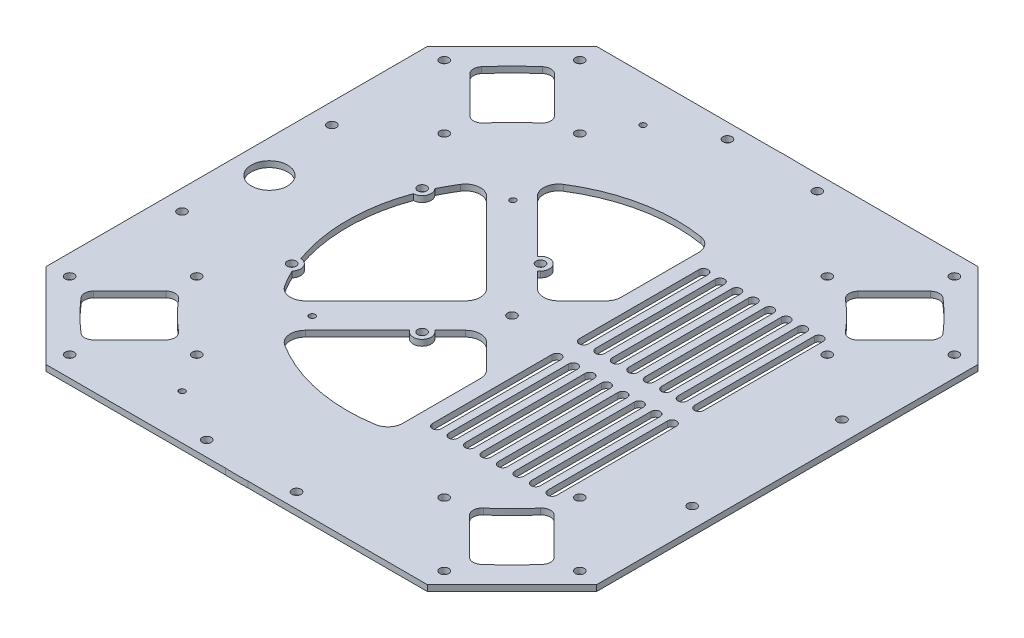
SolidWorks part; units mm, degrees
material "Thornel Mat VMA"
ref_plane "前视基准面" through (0, 0, 0) normal (0, 0, 1) x (1, 0, 0)
ref_plane "上视基准面" through (0, 0, 0) normal (0, 1, 0) x (1, 0, 0)
ref_plane "右视基准面" through (0, 0, 0) normal (1, 0, 0) x (0, 0, -1)
sketch "草图1" plane through (0, 0, 0) normal (0, 1, 0) x (1, 0, 0)
  line L0 (-63.6396, 91.9239) -> (-91.9239, 63.6396)
  line L1 (63.6396, 91.9239) -> (-63.6396, 91.9239)
  line L2 (91.9239, 63.6396) -> (91.9239, -63.6396)
  line L3 (63.6396, -91.9239) -> (-63.6396, -91.9239)
  line L4 (-91.9239, 63.6396) -> (-91.9239, -63.6396)
  line L5 (91.9239, 91.9239) -> (-91.9239, -91.9239) construction
  line L6 (91.9239, -91.9239) -> (-91.9239, 91.9239) construction
  line L7 (91.9239, -63.6396) -> (63.6396, -91.9239)
  line L8 (-91.9239, -63.6396) -> (-63.6396, -91.9239)
  line L9 (63.6396, 91.9239) -> (91.9239, 63.6396)
  line L10 (-91.9239, 91.9239) -> (-91.9239, -91.9239) construction
  line L11 (-91.9239, -91.9239) -> (91.9239, -91.9239) construction
  line L12 (91.9239, -91.9239) -> (91.9239, 91.9239) construction
  line L13 (91.9239, 91.9239) -> (-91.9239, 91.9239) construction
  point P0 (0, 0)
  dimension "D1" = 220
  dimension "D2" = 40
extrude "凸台-拉伸1" add sketch "草图1" along normal blind 2
sketch "草图15" plane through (0, 2, 0) normal (0, 1, 0) x (1, 0, 0)
  line L1 (-40.3412, 82.6837) -> (-31.9185, 62.6852)
  line L2 (44.6358, 80.4465) -> (36.2732, 60.2701)
  line L3 (-42.4295, -81.6317) -> (-34.5316, -61.2845)
  line L4 (41.391, -82.1632) -> (34.5498, -61.2743)
  arc A0 (-42.4295, -81.6317) -> (41.391, -82.1632) centre (0, 0) ccw
  arc A2 (-34.5316, -61.2845) -> (34.5498, -61.2743) centre (0, 0) ccw
  arc A3 (36.2732, 60.2701) -> (-31.9185, 62.6852) centre (0, 0) ccw
  arc A4 (44.6358, 80.4465) -> (-40.3412, 82.6837) centre (0, 0) ccw
  dimension "D1" = 92
extrude "凸台-拉伸3" add sketch "草图15" against normal up to surface (2 mm away) up to face at (0, 0, 0)
sketch "草图18" plane through (0, 2, 0) normal (0, 1, 0) x (1, 0, 0)
  line L0 (-44.0207, 0) -> (12.6253, 0) construction
  line L3 (-54.0207, 0) -> (-91.9239, 0) construction
  line L4 (-91.9239, 63.6396) -> (-91.9239, -63.6396) construction
  line L5 (-4.5, -10) -> (4.5, -10) construction
  line L9 (-4.5, 10) -> (4.5, -10) construction
  line L10 (-4.5, -10) -> (4.5, 10) construction
  line L11 (-4.5, 10) -> (4.5, 10) construction
  circle A9 centre (0, 0) radius 1.5
  point P3 (0, 0)
  point P15 (0, 0)
extrude "切除-拉伸5" cut sketch "草图18" against normal through all both and the other way through all
sketch "草图20" plane through (0, 0, 0) normal (0, -1, 0) x (1, 0, 0)
  line L0 (-45.8783, 0) -> (57.9239, 0) construction
  line L1 (57.9239, 44.5) -> (57.9239, 4.5) construction
  line L2 (59.4239, 44.5) -> (59.4239, 4.5)
  line L3 (56.4239, 44.5) -> (56.4239, 4.5)
  line L4 (57.9239, -44.5) -> (57.9239, -4.5) construction
  line L5 (59.4239, -44.5) -> (59.4239, -4.5)
  line L6 (56.4239, -44.5) -> (56.4239, -4.5)
  line L7 (52.4239, 44.5) -> (52.4239, 4.5) construction
  line L8 (53.9239, 44.5) -> (53.9239, 4.5)
  line L9 (50.9239, 44.5) -> (50.9239, 4.5)
  line L10 (52.4239, -44.5) -> (52.4239, -4.5) construction
  line L11 (53.9239, -44.5) -> (53.9239, -4.5)
  line L12 (50.9239, -44.5) -> (50.9239, -4.5)
  line L13 (46.9239, 44.5) -> (46.9239, 4.5) construction
  line L14 (48.4239, 44.5) -> (48.4239, 4.5)
  line L15 (45.4239, 44.5) -> (45.4239, 4.5)
  line L16 (46.9239, -44.5) -> (46.9239, -4.5) construction
  line L17 (48.4239, -44.5) -> (48.4239, -4.5)
  line L18 (45.4239, -44.5) -> (45.4239, -4.5)
  line L19 (41.4239, 44.5) -> (41.4239, 4.5) construction
  line L20 (42.9239, 44.5) -> (42.9239, 4.5)
  line L21 (39.9239, 44.5) -> (39.9239, 4.5)
  line L22 (41.4239, -44.5) -> (41.4239, -4.5) construction
  line L23 (42.9239, -44.5) -> (42.9239, -4.5)
  line L24 (39.9239, -44.5) -> (39.9239, -4.5)
  line L25 (35.9239, 44.5) -> (35.9239, 4.5) construction
  line L26 (37.4239, 44.5) -> (37.4239, 4.5)
  line L27 (34.4239, 44.5) -> (34.4239, 4.5)
  line L28 (35.9239, -44.5) -> (35.9239, -4.5) construction
  line L29 (37.4239, -44.5) -> (37.4239, -4.5)
  line L30 (34.4239, -44.5) -> (34.4239, -4.5)
  line L31 (30.4239, 44.5) -> (30.4239, 4.5) construction
  line L32 (31.9239, 44.5) -> (31.9239, 4.5)
  line L33 (28.9239, 44.5) -> (28.9239, 4.5)
  line L34 (30.4239, -44.5) -> (30.4239, -4.5) construction
  line L35 (31.9239, -44.5) -> (31.9239, -4.5)
  line L36 (28.9239, -44.5) -> (28.9239, -4.5)
  line L37 (24.9239, 44.5) -> (24.9239, 4.5) construction
  line L38 (26.4239, 44.5) -> (26.4239, 4.5)
  line L39 (23.4239, 44.5) -> (23.4239, 4.5)
  line L40 (24.9239, -44.5) -> (24.9239, -4.5) construction
  line L41 (26.4239, -44.5) -> (26.4239, -4.5)
  line L42 (23.4239, -44.5) -> (23.4239, -4.5)
  line L43 (19.4239, 44.5) -> (19.4239, 4.5) construction
  line L44 (20.9239, 44.5) -> (20.9239, 4.5)
  line L45 (17.9239, 44.5) -> (17.9239, 4.5)
  line L46 (19.4239, -44.5) -> (19.4239, -4.5) construction
  line L47 (20.9239, -44.5) -> (20.9239, -4.5)
  line L48 (17.9239, -44.5) -> (17.9239, -4.5)
  line L49 (91.9239, 63.6396) -> (91.9239, -63.6396) construction
  line L382 (13.9239, -44.5) -> (13.9239, -4.5) construction
  line L383 (12.4239, -44.5) -> (12.4239, -4.5) [skipped]
  line L384 (15.4239, -44.5) -> (15.4239, -4.5) [skipped]
  line L385 (13.9239, 44.5) -> (13.9239, 4.5) construction
  line L386 (15.4239, 44.5) -> (15.4239, 4.5) [skipped]
  line L387 (12.4239, 44.5) -> (12.4239, 4.5) [skipped]
  line L388 (13.9239, -44.5) -> (13.9239, -4.5) construction
  line L389 (12.4239, -44.5) -> (12.4239, -4.5) [skipped]
  line L390 (15.4239, -44.5) -> (15.4239, -4.5) [skipped]
  line L391 (13.9239, 44.5) -> (13.9239, 4.5) construction
  line L392 (15.4239, 44.5) -> (15.4239, 4.5) [skipped]
  line L393 (12.4239, 44.5) -> (12.4239, 4.5) [skipped]
  arc A0 (59.4239, 44.5) -> (56.4239, 44.5) centre (57.9239, 44.5) ccw
  arc A1 (56.4239, 4.5) -> (59.4239, 4.5) centre (57.9239, 4.5) ccw
  arc A2 (59.4239, -44.5) -> (56.4239, -44.5) centre (57.9239, -44.5) cw
  arc A3 (56.4239, -4.5) -> (59.4239, -4.5) centre (57.9239, -4.5) cw
  arc A4 (53.9239, 44.5) -> (50.9239, 44.5) centre (52.4239, 44.5) ccw
  arc A5 (50.9239, 4.5) -> (53.9239, 4.5) centre (52.4239, 4.5) ccw
  arc A6 (53.9239, -44.5) -> (50.9239, -44.5) centre (52.4239, -44.5) cw
  arc A7 (50.9239, -4.5) -> (53.9239, -4.5) centre (52.4239, -4.5) cw
  arc A8 (48.4239, 44.5) -> (45.4239, 44.5) centre (46.9239, 44.5) ccw
  arc A9 (45.4239, 4.5) -> (48.4239, 4.5) centre (46.9239, 4.5) ccw
  arc A10 (48.4239, -44.5) -> (45.4239, -44.5) centre (46.9239, -44.5) cw
  arc A11 (45.4239, -4.5) -> (48.4239, -4.5) centre (46.9239, -4.5) cw
  arc A12 (42.9239, 44.5) -> (39.9239, 44.5) centre (41.4239, 44.5) ccw
  arc A13 (39.9239, 4.5) -> (42.9239, 4.5) centre (41.4239, 4.5) ccw
  arc A14 (42.9239, -44.5) -> (39.9239, -44.5) centre (41.4239, -44.5) cw
  arc A15 (39.9239, -4.5) -> (42.9239, -4.5) centre (41.4239, -4.5) cw
  arc A16 (37.4239, 44.5) -> (34.4239, 44.5) centre (35.9239, 44.5) ccw
  arc A17 (34.4239, 4.5) -> (37.4239, 4.5) centre (35.9239, 4.5) ccw
  arc A18 (37.4239, -44.5) -> (34.4239, -44.5) centre (35.9239, -44.5) cw
  arc A19 (34.4239, -4.5) -> (37.4239, -4.5) centre (35.9239, -4.5) cw
  arc A20 (31.9239, 44.5) -> (28.9239, 44.5) centre (30.4239, 44.5) ccw
  arc A21 (28.9239, 4.5) -> (31.9239, 4.5) centre (30.4239, 4.5) ccw
  arc A22 (31.9239, -44.5) -> (28.9239, -44.5) centre (30.4239, -44.5) cw
  arc A23 (28.9239, -4.5) -> (31.9239, -4.5) centre (30.4239, -4.5) cw
  arc A24 (26.4239, 44.5) -> (23.4239, 44.5) centre (24.9239, 44.5) ccw
  arc A25 (23.4239, 4.5) -> (26.4239, 4.5) centre (24.9239, 4.5) ccw
  arc A26 (26.4239, -44.5) -> (23.4239, -44.5) centre (24.9239, -44.5) cw
  arc A27 (23.4239, -4.5) -> (26.4239, -4.5) centre (24.9239, -4.5) cw
  arc A28 (20.9239, 44.5) -> (17.9239, 44.5) centre (19.4239, 44.5) ccw
  arc A29 (17.9239, 4.5) -> (20.9239, 4.5) centre (19.4239, 4.5) ccw
  arc A30 (20.9239, -44.5) -> (17.9239, -44.5) centre (19.4239, -44.5) cw
  arc A31 (17.9239, -4.5) -> (20.9239, -4.5) centre (19.4239, -4.5) cw
  arc A258 (12.4239, -44.5) -> (15.4239, -44.5) centre (13.9239, -44.5) ccw [skipped]
  arc A259 (15.4239, -4.5) -> (12.4239, -4.5) centre (13.9239, -4.5) ccw [skipped]
  arc A260 (15.4239, 44.5) -> (12.4239, 44.5) centre (13.9239, 44.5) ccw [skipped]
  arc A261 (12.4239, 4.5) -> (15.4239, 4.5) centre (13.9239, 4.5) ccw [skipped]
  point P5 (57.9239, 24.5)
  point P11 (57.9239, 3)
  point P13 (57.9239, -24.5)
  point P18 (57.9239, -3)
  point P19 (79.1207, 0)
  point P23 (52.4239, 24.5)
  point P29 (52.4239, 3)
  point P31 (52.4239, -24.5)
  point P36 (52.4239, -3)
  point P39 (46.9239, 24.5)
  point P45 (46.9239, 3)
  point P47 (46.9239, -24.5)
  point P52 (46.9239, -3)
  point P55 (41.4239, 24.5)
  point P61 (41.4239, 3)
  point P63 (41.4239, -24.5)
  point P68 (41.4239, -3)
  point P71 (35.9239, 24.5)
  point P77 (35.9239, 3)
  point P79 (35.9239, -24.5)
  point P84 (35.9239, -3)
  point P87 (30.4239, 24.5)
  point P93 (30.4239, 3)
  point P95 (30.4239, -24.5)
  point P100 (30.4239, -3)
  point P103 (24.9239, 24.5)
  point P109 (24.9239, 3)
  point P111 (24.9239, -24.5)
  point P116 (24.9239, -3)
  point P119 (19.4239, 24.5)
  point P125 (19.4239, 3)
  point P127 (19.4239, -24.5)
  point P132 (19.4239, -3)
  point P135 (21.0655, -24.0622)
  point P140 (13.9239, -3)
  point P142 (13.9239, 3)
  point P149 (21.0655, 24.0622)
  point P157 (21.0655, -24.0622)
  point P164 (21.0655, 24.0622)
  point P171 (21.0655, -24.0622)
  point P178 (21.0655, 24.0622)
  point P185 (21.0655, -24.0622)
  point P192 (21.0655, 24.0622)
  point P199 (21.0655, -24.0622)
  point P206 (21.0655, 24.0622)
  point P213 (21.0655, -24.0622)
  point P220 (21.0655, 24.0622)
  point P227 (16.1207, -24.0622)
  point P234 (16.1207, 24.0622)
  point P241 (16.1207, -24.0622)
  point P248 (16.1207, 24.0622)
  point P255 (11.1207, -24.0622)
  point P262 (11.1207, 24.0622)
  point P269 (11.1207, -24.0622)
  point P276 (11.1207, 24.0622)
  point P283 (11.1207, -29.0622)
  point P290 (11.1207, 29.0622)
  point P297 (11.1207, -29.0622)
  point P304 (11.1207, 29.0622)
  point P311 (15.1207, -29)
  point P318 (15.1207, 29)
  point P325 (15.1207, -29)
  point P332 (15.1207, 29)
  point P339 (15.1207, -24)
  point P346 (15.1207, 24)
  point P353 (15.1207, -24)
  point P360 (15.1207, 24)
  point P367 (15.1207, -24.5)
  point P374 (15.1207, 24.5)
  point P381 (15.1207, -24.5)
  point P388 (15.1207, 24.5)
  point P395 (15.1207, -24.5)
  point P402 (15.1207, 24.5)
  point P409 (15.1207, -24.5)
  point P416 (15.1207, 24.5)
  point P423 (15.1207, -24.5)
  point P430 (15.1207, 24.5)
  point P437 (15.1207, -24.5)
  point P444 (15.1207, 24.5)
  point P451 (15.1207, -24.5)
  point P458 (15.1207, 24.5)
  point P465 (15.1207, -24.5)
  point P472 (15.1207, 24.5)
  point P479 (15.1207, -24.5)
  point P486 (15.1207, 24.5)
  point P493 (15.1207, -24.5)
  point P500 (15.1207, 24.5)
  point P507 (15.1207, -24.5)
  point P514 (15.1207, 24.5)
  point P521 (15.1207, -24.5)
  point P528 (15.1207, 24.5)
  point P535 (15.1207, -24.5)
  point P542 (15.1207, 24.5)
  point P549 (15.1207, -24.5)
  point P556 (15.1207, 24.5)
  point P563 (15.1207, -24.5)
  point P570 (15.1207, 24.5)
  point P577 (15.1207, -24.5)
  point P584 (15.1207, 24.5)
  point P591 (15.1207, -24.5)
  point P598 (15.1207, 24.5)
  point P605 (15.1207, -24.5)
  point P612 (15.1207, 24.5)
  point P619 (15.1207, -24.5)
  point P626 (15.1207, 24.5)
  point P633 (15.1207, -24.5)
  point P640 (15.1207, 24.5)
  point P647 (15.1207, -24.5)
  point P654 (15.1207, 24.5)
  point P661 (15.1207, -24.5)
  point P668 (15.1207, 24.5)
  point P675 (15.1207, -24.5)
  point P682 (15.1207, 24.5)
  point P689 (15.1207, -24.5)
  point P696 (15.1207, 24.5)
  point P703 (15.1207, -24.5)
  point P710 (15.1207, 24.5)
  point P717 (15.1207, -24.5)
  point P724 (15.1207, 24.5)
  point P731 (15.1207, -24.5)
  point P738 (15.1207, 24.5)
  point P745 (15.1207, -24.5)
  point P752 (15.1207, 24.5)
  point P759 (15.1207, -24.5)
  point P766 (15.1207, 24.5)
  point P773 (15.1207, -24.5)
  point P780 (15.1207, 24.5)
  point P787 (15.1207, -24.5)
  point P794 (15.1207, 24.5)
  point P801 (15.1207, -24.5)
  point P808 (15.1207, 24.5)
  point P815 (14.4239, -24.5)
  point P822 (14.4239, 24.5)
  point P829 (14.4239, -24.5)
  point P836 (14.4239, 24.5)
  point P843 (13.9239, -24.5)
  point P850 (13.9239, 24.5)
  point P857 (13.9239, -24.5)
  point P864 (13.9239, 24.5)
  point P871 (13.9239, -24.5)
  point P878 (13.9239, 24.5)
  point P885 (13.9239, -24.5)
  point P892 (13.9239, 24.5)
  point P899 (13.9239, -24.5)
  point P906 (13.9239, 24.5)
  point P913 (13.9239, -24.5)
  point P920 (13.9239, 24.5)
  point P927 (13.9239, -24.5)
  point P934 (13.9239, 24.5)
  dimension "D2" = 9
  dimension "D5" = 1.5
  dimension "D1" = 3
  dimension "D3" = 40
  dimension "D4" = 34
  dimension "D6" = 5.5
extrude "切除-拉伸7" cut sketch "草图20" against normal through all both and the other way through all
hole_wizard "孔1" positions "草图27" profile "草图28" legacy end condition through all
sketch "草图27" plane through (0, 2, 0) normal (0, 1, 0) x (1, 0, 0)
  point P0 (-85.1534, 62.5296)
  point P3 (-63.9402, 41.3164)
  point P6 (-62.5259, 85.157)
  point P9 (-41.3127, 63.9438)
  point P12 (41.3127, 63.9438)
  point P15 (62.5259, 85.157)
  point P18 (85.1534, 62.5296)
  point P21 (63.9402, 41.3164)
  point P24 (63.9402, -41.3091)
  point P27 (85.1534, -62.5223)
  point P36 (62.5259, -85.1497)
  point P39 (41.3127, -63.9365)
  point P42 (-85.1534, -62.5223)
  point P45 (-63.9402, -41.3091)
  point P48 (-41.3127, -63.9365)
  point P51 (-62.5259, -85.1497)
sketch "草图28" plane through (-85.1534, 2, -62.5296) normal (1, 0, 0) x (0, 0, 1)
  line L0 (0, 0) -> (0, 2)
  line L1 (0, 2) -> (1.5, 2)
  line L2 (1.5, 2) -> (1.5, 0)
  line L3 (1.5, 0) -> (0, 0)
  line L4 (0, 110) -> (0, -10) construction
  dimension "直径" = 3
  dimension "深度" = 2
sketch "草图31" plane through (0, 2, 0) normal (0, 1, 0) x (1, 0, 0)
  line L0 (-62.7269, 76.9258) -> (-50.6692, 64.8681)
  line L1 (-50.7195, 64.8107) -> (-62.7268, 76.9107) construction
  line L2 (-76.8731, 62.7876) -> (-64.8163, 50.7308)
  line L3 (-76.8882, 62.7878) -> (-64.8737, 50.6805) construction
  line L4 (76.9258, 62.7269) -> (64.8681, 50.6692)
  line L5 (62.7876, 76.8731) -> (50.7308, 64.8163)
  line L6 (62.7269, -76.9258) -> (50.6692, -64.8681)
  line L7 (76.8731, -62.7876) -> (64.8163, -50.7308)
  line L8 (-76.9258, -62.7269) -> (-64.8681, -50.6692)
  line L9 (-62.7876, -76.8731) -> (-50.7308, -64.8163)
  line L10 (41.3127, 63.9438) -> (62.5259, 85.157) construction
  arc A0 (-66.8133, 77.0713) -> (-77.017, 66.8759) centre (0, 0) ccw
  arc A1 (-50.8592, 60.4512) -> (-60.4012, 50.9185) centre (0, 0) ccw
  arc A2 (-62.7269, 76.9258) -> (-66.8133, 77.0713) centre (-64.8482, 74.8045) ccw
  arc A3 (-50.8592, 60.4512) -> (-50.6692, 64.8681) centre (-52.7905, 62.7468) ccw
  arc A4 (-60.4012, 50.9185) -> (-64.8163, 50.7308) centre (-62.695, 52.8521) cw
  arc A5 (-76.8731, 62.7876) -> (-77.017, 66.8759) centre (-74.7518, 64.9089) cw
  arc A6 (77.0713, 66.8133) -> (66.8759, 77.017) centre (0, 0) ccw
  arc A7 (60.4512, 50.8592) -> (50.9185, 60.4012) centre (0, 0) ccw
  arc A8 (76.9258, 62.7269) -> (77.0713, 66.8133) centre (74.8045, 64.8482) ccw
  arc A9 (60.4512, 50.8592) -> (64.8681, 50.6692) centre (62.7468, 52.7905) ccw
  arc A10 (50.9185, 60.4012) -> (50.7308, 64.8163) centre (52.8521, 62.695) cw
  arc A11 (62.7876, 76.8731) -> (66.8759, 77.017) centre (64.9089, 74.7518) cw
  arc A12 (66.8133, -77.0713) -> (77.017, -66.8759) centre (0, 0) ccw
  arc A13 (50.8592, -60.4512) -> (60.4012, -50.9185) centre (0, 0) ccw
  arc A14 (62.7269, -76.9258) -> (66.8133, -77.0713) centre (64.8482, -74.8045) ccw
  arc A15 (50.8592, -60.4512) -> (50.6692, -64.8681) centre (52.7905, -62.7468) ccw
  arc A16 (60.4012, -50.9185) -> (64.8163, -50.7308) centre (62.695, -52.8521) cw
  arc A17 (76.8731, -62.7876) -> (77.017, -66.8759) centre (74.7518, -64.9089) cw
  arc A18 (-77.0713, -66.8133) -> (-66.8759, -77.017) centre (0, 0) ccw
  arc A19 (-60.4512, -50.8592) -> (-50.9185, -60.4012) centre (0, 0) ccw
  arc A20 (-76.9258, -62.7269) -> (-77.0713, -66.8133) centre (-74.8045, -64.8482) ccw
  arc A21 (-60.4512, -50.8592) -> (-64.8681, -50.6692) centre (-62.7468, -52.7905) ccw
  arc A22 (-50.9185, -60.4012) -> (-50.7308, -64.8163) centre (-52.8521, -62.695) cw
  arc A23 (-62.7876, -76.8731) -> (-66.8759, -77.017) centre (-64.9089, -74.7518) cw
  point P13 (-64.6752, 78.8741)
  point P20 (-78.823, 64.7375)
  point P22 (-60.4087, -50.9097)
  point P59 (0, 0)
  dimension "D1" = 3
  dimension "D3" = 102
  dimension "D4" = 79
  dimension "D2" = 4
extrude "切除-拉伸14" cut sketch "草图31" against normal through all both and the other way through all
sketch "草图32" plane through (0, 2, 0) normal (0, 1, 0) x (1, 0, 0)
  circle A0 centre (-80.9686, 0) radius 6.05
  circle A1 centre (-80.9686, 0) radius 6.05 construction
extrude "切除-拉伸15" cut sketch "草图32" against normal through all both and the other way through all
hole_wizard "孔3" positions "草图34" profile "草图35" legacy end condition through all
sketch "草图34" plane through (0, 2, 0) normal (0, 1, 0) x (1, 0, 0)
  circle A0 centre (85.1534, -25) radius 1.5 construction
  circle A1 centre (85.1534, 25) radius 1.5 construction
  circle A2 centre (-85.1534, -25) radius 1.5 construction
  circle A3 centre (-85.1534, 25) radius 1.5 construction
  point P0 (-85.1534, 25)
  point P2 (-85.1534, -25)
  point P4 (-15, 86.9239)
  point P6 (15, 86.9239)
  point P8 (85.1534, 25)
  point P10 (85.1534, -25)
  point P12 (-15, -86.9239)
  point P14 (15, -86.9239)
  point P17 (0, 0)
  point P20 (0, 0)
  point P23 (0, 0)
  point P26 (0, 0)
sketch "草图35" plane through (-85.1534, 2, -25) normal (1, 0, 0) x (0, 0, 1)
  line L0 (0, 0) -> (0, 2)
  line L1 (0, 2) -> (1.5, 2)
  line L2 (1.5, 2) -> (1.5, 0)
  line L3 (1.5, 0) -> (0, 0)
  line L4 (0, 110) -> (0, -10) construction
  dimension "直径" = 3
  dimension "深度" = 2
sketch "草图36" plane through (0, 2, 0) normal (0, 1, 0) x (1, 0, 0)
  line L1 (-4.2426, -4.2426) -> (0, 0) construction
  line L2 (11.4594, -19.9447) -> (3.5355, -12.0208)
  line L6 (0, 0) -> (-34.4161, 42.9014) construction
  line L7 (-42.9014, 34.4161) -> (0, 0) construction
  line L8 (3.5355, 12.0208) -> (11.4594, 19.9447)
  line L9 (-8.4853, 0) -> (0, -8.4853) construction
  line L10 (0, -8.4853) -> (8.4853, 0) construction
  line L11 (8.4853, 0) -> (0, 8.4853) construction
  line L12 (0, 0) -> (-42.9014, -34.4161) construction
  line L13 (0, 0) -> (-34.4161, -42.9014) construction
  line L14 (-12.0208, -3.5355) -> (-38.7318, -30.2465)
  line L15 (-12.0208, 3.5355) -> (-38.7318, 30.2465)
  line L16 (-3.5355, 12.0208) -> (-30.2465, 38.7318)
  line L17 (12.9239, 49.3681) -> (12.9239, 23.4802)
  line L18 (12.9239, -23.4802) -> (12.9239, -49.3681)
  line L19 (-3.5355, -12.0208) -> (-30.2465, -38.7318)
  line L20 (17.9239, 4.5) -> (17.9239, 44.5) construction
  line L21 (-8.4853, 0) -> (0, 8.4853) construction
  line L22 (-8.4853, 0) -> (8.4853, 0) construction
  line L23 (0, 8.4853) -> (0, -8.4853) construction
  arc A0 (8.7163, 54.3049) -> (-29.382, 46.494) centre (0, 0) ccw
  arc A1 (-46.494, 29.382) -> (-46.494, -29.382) centre (0, 0) ccw
  arc A2 (12.9239, -49.3681) -> (8.7163, -54.3049) centre (7.9239, -49.3681) cw
  arc A3 (-29.382, -46.494) -> (-30.2465, -38.7318) centre (-26.711, -42.2673) cw
  arc A4 (-38.7318, -30.2465) -> (-46.494, -29.382) centre (-42.2673, -26.711) cw
  arc A5 (-38.7318, 30.2465) -> (-46.494, 29.382) centre (-42.2673, 26.711) ccw
  arc A6 (-29.382, -46.494) -> (8.7163, -54.3049) centre (0, 0) ccw
  arc A7 (12.9239, 49.3681) -> (8.7163, 54.3049) centre (7.9239, 49.3681) ccw
  arc A8 (-30.2465, 38.7318) -> (-29.382, 46.494) centre (-26.711, 42.2673) cw
  arc A9 (12.9239, -23.4802) -> (11.4594, -19.9447) centre (7.9239, -23.4802) ccw
  arc A10 (11.4594, 19.9447) -> (12.9239, 23.4802) centre (7.9239, 23.4802) ccw
  arc A11 (3.5355, -12.0208) -> (-3.5355, -12.0208) centre (0, -15.5563) ccw
  arc A12 (-12.0208, -3.5355) -> (-12.0208, 3.5355) centre (-15.5563, 0) ccw
  arc A13 (3.5355, 12.0208) -> (-3.5355, 12.0208) centre (0, 15.5563) cw
  point P1 (-4.2426, -4.2426)
  point P4 (0, 0)
  point P10 (0, 0)
  point P40 (12.9239, 21.4092)
  dimension "D1" = 110
  dimension "D4" = 5
  dimension "D2" = 12
  dimension "D3" = 5
extrude "切除-拉伸16" cut sketch "草图36" against normal blind 10
hole_wizard "孔4" positions "草图38" profile "草图39" legacy end condition through all
sketch "草图38" plane through (0, 2, 0) normal (0, 1, 0) x (1, 0, 0)
  line L0 (0, 0) -> (-33.1949, 0) construction
  line L2 (-33.1949, 33.5) -> (-33.1949, -33.5) construction
  line L4 (-28.1949, 20.4396) -> (-28.1949, 94.4396) construction
  line L5 (-3.7417, 91.9239) -> (-63.6396, 91.9239) construction
  line L6 (-63.6396, -91.9239) -> (-3.7417, -91.9239) construction
  point P5 (-33.1949, 33.5)
  point P6 (-33.1949, -33.5)
  point P15 (-33.1949, 76.9239)
  point P17 (-33.1949, -76.9239)
  point P21 (-33.1949, -79.1058)
  point P22 (-33.1949, 72.1124)
  dimension "D1" = 5
  dimension "D2" = 67
  dimension "D3" = 15
  dimension "D4" = 15
sketch "草图39" plane through (-33.1949, 2, 76.9239) normal (1, 0, 0) x (0, 0, 1)
  line L0 (0, 0) -> (0, 2)
  line L1 (0, 2) -> (1, 2)
  line L2 (1, 2) -> (1, 0)
  line L3 (1, 0) -> (0, 0)
  line L4 (0, 110) -> (0, -10) construction
  dimension "直径" = 2
  dimension "深度" = 2
sketch "草图40" plane through (0, 2, 0) normal (0, 1, 0) x (1, 0, 0)
  line L0 (-52.6274, 22.6274) -> (-49.3406, 19.3406) construction
  line L1 (-12.1456, 17.8544) -> (-6.2766, 23.7234) construction
  line L2 (-12.3577, 21.885) -> (-14.1806, 20.062)
  line L3 (-9.4939, 24.7487) -> (-14.3933, 19.8493) construction
  line L4 (-14.1806, 20.062) -> (-12.2509, 15.8501)
  line L5 (-12.2509, 15.8501) -> (-9.162, 16.5953)
  line L6 (-10.1507, 15.6067) -> (-5.2513, 20.5061) construction
  line L7 (-9.162, 16.5953) -> (-8.115, 17.6423)
  line L8 (0, 0) -> (-55, 0) construction
  line L9 (-12.1456, -17.8544) -> (-6.2766, -23.7234) construction
  line L10 (-52.6274, -22.6274) -> (-49.3406, -19.3406) construction
  line L11 (-9.162, -16.5953) -> (-8.115, -17.6423)
  line L12 (-12.2509, -15.8501) -> (-9.162, -16.5953)
  line L13 (-14.1806, -20.062) -> (-12.2509, -15.8501)
  line L14 (-12.3577, -21.885) -> (-14.1806, -20.062)
  arc A0 (-51.5314, 23.7234) -> (-53.7234, 21.5314) centre (-52.6274, 22.6274) ccw construction
  circle A1 centre (-51.7789, 21.7789) radius 3
  arc A2 (-12.1456, 20.0465) -> (-9.9535, 17.8544) centre (-11.0495, 18.9505) ccw construction
  arc A3 (-6.2766, 21.5314) -> (-8.4686, 23.7234) centre (-7.3726, 22.6274) ccw construction
  arc A4 (-8.115, 17.6423) -> (-12.3577, 21.885) centre (-10.2364, 19.7636) ccw
  arc A5 (-46.494, 29.382) -> (-46.494, -29.382) centre (0, 0) ccw construction
  arc A6 (-8.115, -17.6423) -> (-12.3577, -21.885) centre (-10.2364, -19.7636) cw
  circle A7 centre (-51.7789, -21.7789) radius 3
  dimension "D1" = 6
  dimension "D2" = 1.2
  dimension "D3" = 2.7
extrude "凸台-拉伸4" add sketch "草图40" against normal blind 2
hole_wizard "孔5" positions "草图41" profile "草图42" legacy end condition through all
sketch "草图41" plane through (0, 2, 0) normal (0, 1, 0) x (1, 0, 0)
  line L0 (-55, 0) -> (0, 0) construction
  arc A0 (-51.6944, 18.7801) -> (-49.5763, 23.8157) centre (-51.7789, 21.7789) ccw construction
  arc A1 (-8.115, 17.6423) -> (-12.3577, 21.885) centre (-10.2364, 19.7636) ccw construction
  arc A2 (-51.6944, 18.7801) -> (-51.6944, -18.7801) centre (0, 0) ccw construction
  point P0 (-51.7789, 21.7789)
  point P9 (-10.2364, 19.7636)
  point P23 (-10.2364, -19.7636)
  point P24 (-51.7789, -21.7789)
sketch "草图42" plane through (-51.7789, 2, -21.7789) normal (1, 0, 0) x (0, 0, 1)
  line L0 (0, 0) -> (0, 2)
  line L1 (0, 2) -> (1.5, 2)
  line L2 (1.5, 2) -> (1.5, 0)
  line L3 (1.5, 0) -> (0, 0)
  line L4 (0, 110) -> (0, -10) construction
  dimension "直径" = 3
  dimension "深度" = 2
